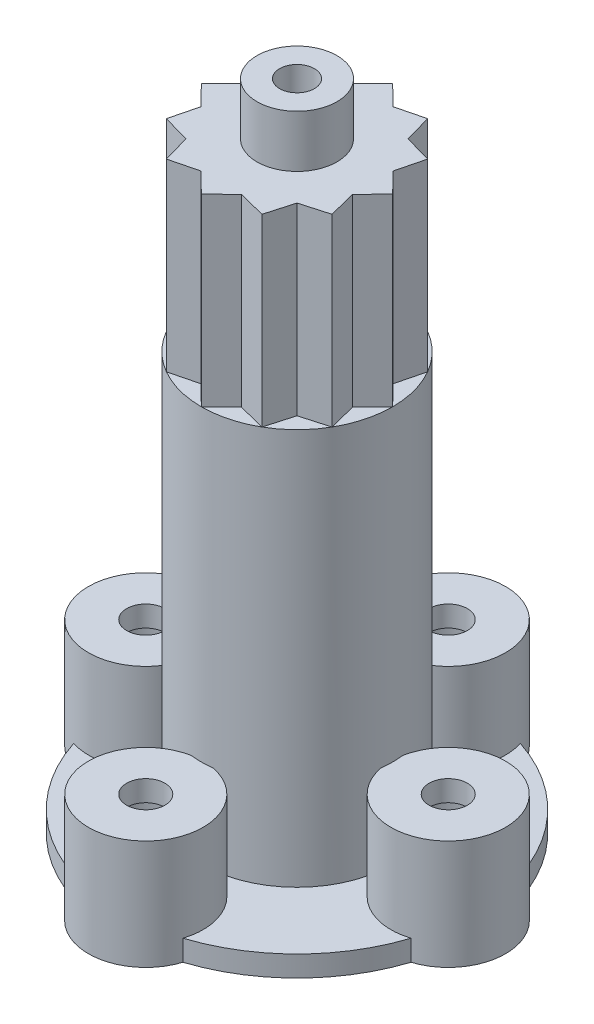
SolidWorks part; units mm, degrees
ref_plane "Front Plane" through (0, 0, 0) normal (0, 0, 1) x (1, 0, 0)
ref_plane "Top Plane" through (0, 0, 0) normal (0, 1, 0) x (1, 0, 0)
ref_plane "Right Plane" through (0, 0, 0) normal (1, 0, 0) x (0, 0, -1)
sketch "Sketch1" plane through (0, 0, 0) normal (0, 1, 0) x (1, 0, 0)
  circle A0 centre (0, 0) radius 10.2
  dimension "D1" = 20.4
extrude "Boss-Extrude1" add sketch "Sketch1" along normal blind 1.2
sketch "Sketch3" plane through (0, 1.2, 0) normal (0, 1, 0) x (1, 0, 0)
  circle A0 centre (0, 0) radius 5.5
  dimension "D1" = 11
extrude "Boss-Extrude2" add sketch "Sketch3" along normal blind 22.8
sketch "Sketch6" plane through (0, 0, 0) normal (0, -1, 0) x (1, 0, 0)
  line L0 (12.265, 0) -> (-12.265, 0) construction
  circle A0 centre (8.7, 0) radius 3.3
  point P4 (9.2337, 0)
  point P5 (0, 0)
  dimension "D1" = 6.6
extrude "Boss-Extrude7" add sketch "Sketch6" against normal blind 6.3 contours A0
ref_axis "Axis1" through (0, 25.2, 0) along (0, -1, 0)
sketch "Sketch7" plane through (0, 0, 0) normal (0, -1, 0) x (1, 0, 0)
  circle A0 centre (8.7, 0) radius 2.2
  point P3 (0, 0)
  point P4 (0, 0)
  point P5 (0, 0)
  point P6 (0, 0)
  point P7 (0, 0)
  point P8 (0, 0)
  point P9 (0, 0)
  dimension "D1" = 4.4
extrude "Cut-Extrude1" cut sketch "Sketch7" against normal blind 5.1
sketch "Sketch8" plane through (0, 6.3, 0) normal (0, 1, 0) x (1, 0, 0)
  circle A0 centre (8.7, 0) radius 1.1
  dimension "D1" = 2.2
extrude "Cut-Extrude2" cut sketch "Sketch8" against normal blind 1.2
pattern_circular "CirPattern1" count 4 over 360 about axis through (0, 25.2, 0) along (0, -1, 0) of "Boss-Extrude7", "Cut-Extrude1", "Cut-Extrude2"
sketch "Sketch9" plane through (0, 0, 0) normal (0, -1, 0) x (-1, 0, 0)
  circle A0 centre (0, 0) radius 4.4
  dimension "D1" = 8.8
extrude "Cut-Extrude3" cut sketch "Sketch9" against normal blind 22.8
sketch "Sketch10" plane through (0, 24, 0) normal (0, 1, 0) x (1, 0, 0)
  circle A0 centre (0, 0) radius 4.5
  dimension "D1" = 9
extrude "Boss-Extrude8" add sketch "Sketch10" along normal blind 10.6
sketch "Sketch11" plane through (0, 24, 0) normal (0, 1, 0) x (1, 0, 0)
  line L0 (-1.2, 4.337) -> (1.2, 4.337)
  line L1 (1.2, 4.337) -> (0, 5.5)
  line L2 (0, 5.5) -> (-1.2, 4.337)
  line L3 (1.2, -4.337) -> (-1.2, -4.337) construction
  line L4 (1.2, -4.337) -> (1.2, 4.337) construction
  line L5 (1.2, 4.337) -> (-1.2, 4.337) construction
  line L6 (-1.2, -4.337) -> (-1.2, 4.337) construction
  line L7 (1.2, -4.337) -> (-1.2, 4.337) construction
  line L8 (1.2, 4.337) -> (-1.2, -4.337) construction
  circle A0 centre (0, 0) radius 4.5 construction
  arc A1 (0.6399, 5.4626) -> (-0.6399, 5.4626) centre (0, 0) ccw construction
  point P0 (0, 0)
  point P4 (0, 0)
  dimension "D1" = 2.4
extrude "Boss-Extrude9" add sketch "Sketch11" along normal blind 10.6 contours L2 L0 L1
pattern_circular "CirPattern2" count 12 over 360 about axis through (0, 25.2, 0) along (0, -1, 0) of "Boss-Extrude9"
sketch "Sketch12" plane through (0, 22.8, 0) normal (0, -1, 0) x (1, 0, 0)
  circle A0 centre (0, 0) radius 3.2
  dimension "D1" = 6.4
extrude "Cut-Extrude4" cut sketch "Sketch12" against normal blind 10.6
sketch "Sketch13" plane through (0, 34.6, 0) normal (0, 1, 0) x (1, 0, 0)
  circle A0 centre (0, 0) radius 2.3
  dimension "D1" = 4.6
extrude "Boss-Extrude10" add sketch "Sketch13" along normal blind 3
sketch "Sketch14" plane through (0, 37.6, 0) normal (0, 1, 0) x (1, 0, 0)
  circle A0 centre (0, 0) radius 1
  dimension "D1" = 2
extrude "Cut-Extrude5" cut sketch "Sketch14" against normal blind 3
